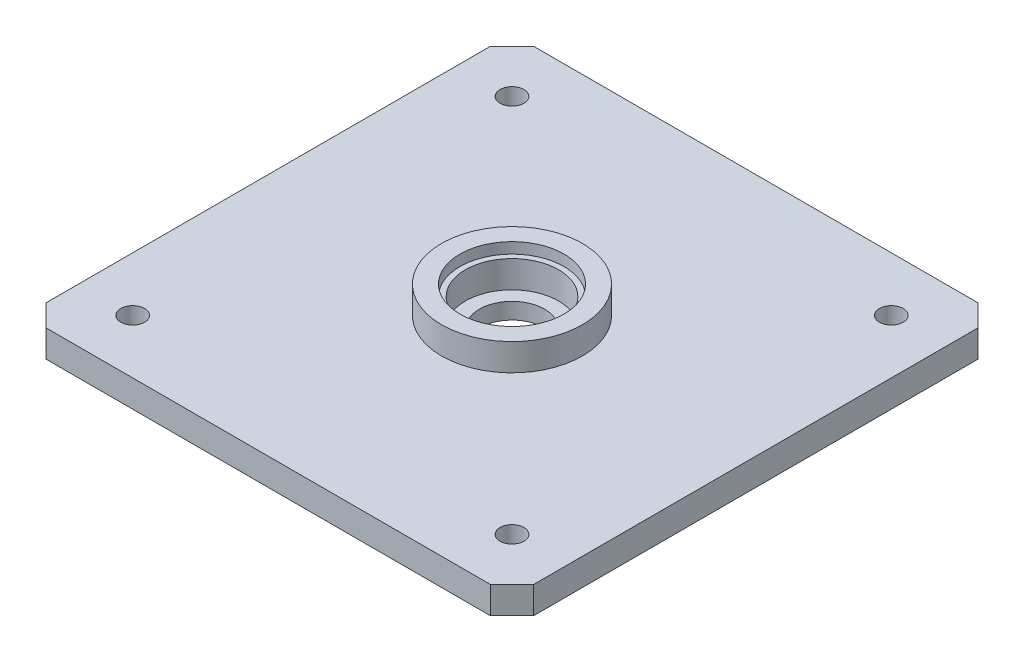
SolidWorks part; units mm, degrees
ref_plane "Front Plane" through (0, 0, 0) normal (0, 0, 1) x (1, 0, 0)
ref_plane "Top Plane" through (0, 0, 0) normal (0, 1, 0) x (1, 0, 0)
ref_plane "Right Plane" through (0, 0, 0) normal (1, 0, 0) x (0, 0, -1)
sketch "Sketch1" plane through (0, 0, 0) normal (0, 1, 0) x (1, 0, 0)
  line L1 (-45, -45) -> (45, -45)
  line L2 (-45, -45) -> (-45, 45)
  line L3 (-45, 45) -> (45, 45)
  line L4 (45, -45) -> (45, 45)
  line L5 (-45, -45) -> (45, 45) construction
  line L6 (-45, 45) -> (45, -45) construction
  circle A0 centre (0, 0) radius 6
  circle A1 centre (0, 0) radius 8.6
  circle A2 centre (0, 0) radius 9.6
  circle A3 centre (0, 0) radius 13
  circle A4 centre (-35, 35) radius 2.2
  circle A5 centre (35, 35) radius 2.2
  circle A6 centre (35, -35) radius 2.2
  circle A7 centre (-35, -35) radius 2.2
  point P0 (0, 0)
  point P13 (32.301, 23.4692)
  point P14 (0, 0)
  point P22 (0, 0)
  dimension "D2" = 12
  dimension "D3" = 17.2
  dimension "D4" = 19.2
  dimension "D5" = 26
  dimension "D6" = 4.4
  dimension "D1" = 90
  dimension "D8" = 10
  dimension "D7" = 4
extrude "Boss-Extrude1" add sketch "Sketch1" along normal blind 5 contours L1 L4 L3 L2 A7 A6 A5 A4 A3 region at (-43.7272, 0, 0)
extrude "Boss-Extrude2" add sketch "Sketch1<3>" along normal blind 3 contours A3 A2 | A2 A1 | A1 A0 region at (-8.3568, 0, 0) region at (-9.3285, 0, 0) region at (-12.6323, 0, 0)
sketch "Sketch1<3>" plane through (0, 0, 0) normal (0, 1, 0) x (1, 0, 0) same geometry as "Sketch1"
extrude "Boss-Extrude3" add sketch "Sketch1<4>" along normal blind 8 contours A2 A1 | A3 A2 region at (-9.3285, 0, 0) region at (-12.6323, 0, 0)
sketch "Sketch1<4>" plane through (0, 0, 0) normal (0, 1, 0) x (1, 0, 0) same geometry as "Sketch1"
extrude "Boss-Extrude4" add sketch "Sketch1<5>" along normal blind 10 contours A3 A2 region at (-12.6323, 0, 0)
sketch "Sketch1<5>" plane through (0, 0, 0) normal (0, 1, 0) x (1, 0, 0) same geometry as "Sketch1"
chamfer "Chamfer1" distance 4 4 edges at (-45, 2.5, -45) (45, 2.5, -45) (-45, 2.5, 45) (45, 2.5, 45)
